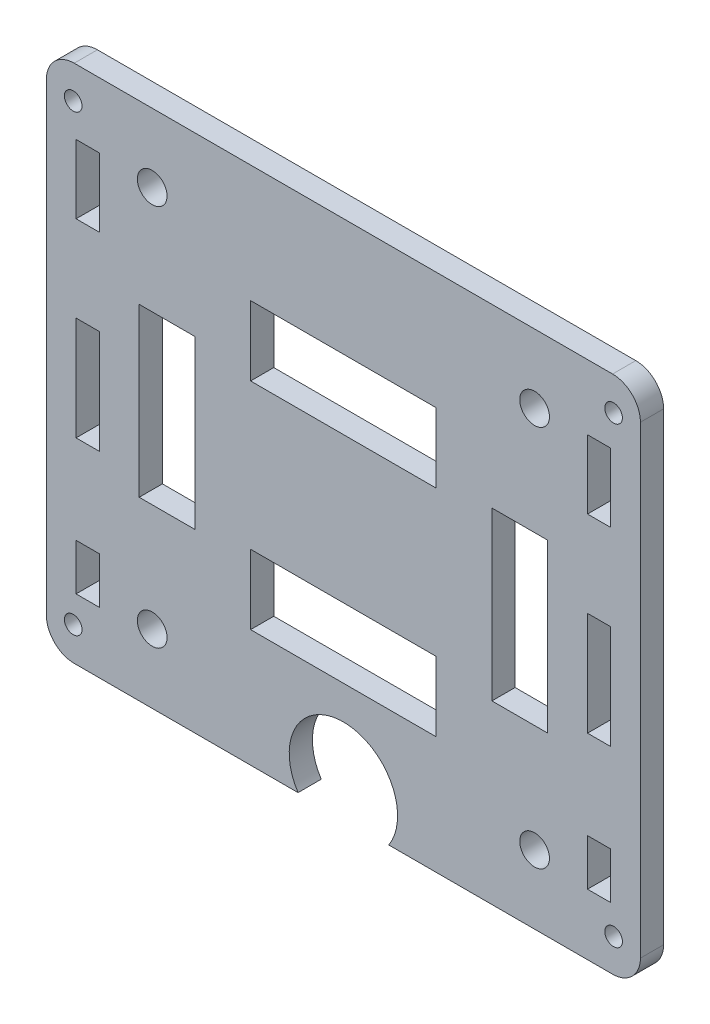
SolidWorks part; units mm, degrees
material "Delrin 2700 NC010, Low Viscosity Acetal Copolymer (SS)"
ref_plane "Front Plane" through (0, 0, 0) normal (0, 0, 1) x (1, 0, 0)
ref_plane "Top Plane" through (0, 0, 0) normal (0, 1, 0) x (1, 0, 0)
ref_plane "Right Plane" through (0, 0, 0) normal (1, 0, 0) x (0, 0, -1)
sketch "Sketch1" plane through (0, 0, 0) normal (0, 0, 1) x (1, 0, 0)
  line L0 (0, -1000) -> (0, 49000) construction
  line L1 (18.415, 17.78) -> (-18.415, 17.78)
  line L2 (20.32, 15.875) -> (20.32, -17.78)
  line L3 (20.32, -17.78) -> (-20.32, -17.78)
  line L4 (-20.32, 15.875) -> (-20.32, -17.78)
  line L5 (20.32, 17.78) -> (-20.32, -17.78) construction
  line L6 (20.32, -17.78) -> (-20.32, 17.78) construction
  line L7 (-1000, 0) -> (49000, 0) construction
  line L9 (10.16, 5.715) -> (13.97, 5.715)
  line L10 (-6.35, -4.9848) -> (6.35, -4.9848)
  line L11 (-6.35, -4.9848) -> (-6.35, -9.7473)
  line L12 (-6.35, -9.7473) -> (6.35, -9.7473)
  line L13 (6.35, -4.9848) -> (6.35, -9.7473)
  line L14 (-6.35, -4.9848) -> (6.35, -9.7473) construction
  line L18 (0, 0) -> (-24.2469, 20.3456) construction
  line L19 (-6.35, -9.7473) -> (6.35, -4.9848) construction
  line L20 (-10.16, 5.715) -> (-13.97, 5.715)
  line L21 (-10.16, 5.715) -> (-10.16, -5.715)
  line L22 (-18.288, 8.625) -> (-16.7005, 8.625)
  line L23 (-18.288, 11.165) -> (-18.288, 8.625)
  line L24 (-16.7005, 11.165) -> (-18.288, 11.165)
  line L25 (-16.7005, 8.625) -> (-16.7005, 11.165)
  line L26 (-10.16, -5.715) -> (-13.97, -5.715)
  line L27 (-13.97, 5.715) -> (-13.97, -5.715)
  line L28 (-10.16, 5.715) -> (-13.97, -5.715) construction
  line L29 (-10.16, -5.715) -> (-13.97, 5.715) construction
  line L30 (10.16, -5.715) -> (13.97, -5.715)
  line L31 (13.97, 5.715) -> (13.97, -5.715)
  line L32 (10.16, 5.715) -> (10.16, -5.715)
  line L33 (-6.35, 4.9848) -> (-6.35, 9.7473)
  line L34 (-6.35, 4.9848) -> (6.35, 4.9848)
  line L35 (-6.35, 9.7473) -> (6.35, 9.7473)
  line L36 (6.35, 4.9848) -> (6.35, 9.7473)
  line L37 (-18.288, 8.625) -> (-16.7005, 8.625)
  line L38 (-18.288, 13.324) -> (-18.288, 8.625)
  line L39 (-16.7005, 11.165) -> (-18.288, 11.165) construction
  line L40 (-16.7005, 8.625) -> (-16.7005, 13.324)
  line L41 (-18.288, -12.457) -> (-16.7005, -12.457)
  line L42 (-18.288, -10.425) -> (-18.288, -12.457)
  line L43 (-16.7005, -10.425) -> (-18.288, -10.425)
  line L44 (-16.7005, -12.457) -> (-16.7005, -10.425)
  line L45 (-18.288, -12.457) -> (-16.7005, -12.457) construction
  line L46 (-18.288, -10.425) -> (-18.288, -13.6)
  line L47 (-16.7005, -10.425) -> (-18.288, -10.425)
  line L48 (-16.7005, -13.6) -> (-16.7005, -10.425)
  line L61 (-18.288, -13.6) -> (-16.7005, -13.6)
  line L62 (-16.7005, 13.324) -> (-18.288, 13.324)
  line L63 (18.288, -12.457) -> (16.7005, -12.457) construction
  line L64 (18.288, -13.6) -> (16.7005, -13.6)
  line L65 (16.7005, -13.6) -> (16.7005, -10.425)
  line L66 (16.7005, -10.425) -> (18.288, -10.425)
  line L67 (18.288, -10.425) -> (18.288, -13.6)
  line L68 (16.7005, 11.165) -> (18.288, 11.165) construction
  line L69 (16.7005, 13.324) -> (18.288, 13.324)
  line L70 (16.7005, 8.625) -> (16.7005, 13.324)
  line L71 (18.288, 13.324) -> (18.288, 8.625)
  line L72 (18.288, 8.625) -> (16.7005, 8.625)
  line L107 (18.288, 2.7432) -> (16.7005, 2.7432)
  line L108 (18.288, -4.3561) -> (16.7005, -4.3561)
  line L109 (18.288, 2.7432) -> (18.288, -4.3561)
  line L110 (16.7005, -4.3561) -> (16.7005, 2.7432)
  line L111 (-16.7005, -4.3561) -> (-16.7005, 2.7432)
  line L112 (-18.288, 2.7432) -> (-18.288, -4.3561)
  line L113 (-18.288, -4.3561) -> (-16.7005, -4.3561)
  line L114 (-18.288, 2.7432) -> (-16.7005, 2.7432)
  circle A0 centre (0, -15.748) radius 3.7084
  circle A1 centre (-18.4847, 15.5105) radius 0.6032
  circle A2 centre (-13.08, -13.08) radius 1.016
  circle A3 centre (18.4847, 15.5105) radius 0.6033
  circle A4 centre (-13.08, 13.08) radius 1.016
  circle A5 centre (13.08, 13.08) radius 1.016
  circle A6 centre (13.08, -13.08) radius 1.016
  arc A7 (18.415, -17.78) -> (20.32, -15.875) centre (18.415, -15.875) ccw
  arc A8 (-18.415, -17.78) -> (-20.32, -15.875) centre (-18.415, -15.875) cw
  arc A9 (-18.415, 17.78) -> (-20.32, 15.875) centre (-18.415, 15.875) ccw
  arc A10 (18.415, 17.78) -> (20.32, 15.875) centre (18.415, 15.875) cw
  circle A11 centre (18.4847, -15.5105) radius 0.6033
  circle A12 centre (-18.4847, -15.5105) radius 0.6032
  point P0 (0, 0)
  point P9 (0, 0)
  point P11 (0, -7.366)
  point P53 (-12.065, 0)
  dimension "D6" = 7.4168
  dimension "D7" = 1.2065
  dimension "D9" = 2.032
  dimension "D12" = 0
  dimension "D13" = 0
  dimension "D14" = 1.905
  dimension "D15" = 1.905
  dimension "D1" = 35.56
  dimension "D2" = 40.64
  dimension "D3" = 4.7625
  dimension "D4" = 12.7
  dimension "D5" = 15.748
  dimension "D8" = 24.13
  dimension "D10" = 13.08
  dimension "D11" = 13.08
  dimension "D17" = 2.159
  dimension "D18" = 7.0993
  dimension "D16" = 1.143
  dimension "D19" = 40
  dimension "D20" = 8.382
  dimension "D21" = 3.81
  dimension "D22" = 11.43
  dimension "D23" = 12.065
  dimension "D24" = 1.5875
  dimension "D25" = 2.7432
extrude "Boss-Extrude1" add sketch "Sketch1" along normal blind 1.5875 contours A10 L1 A9 L4 L3 A0 L2 A6 A5 A4 L12 A1 A2 A3 region at (0, 0.4596, 0)
ref_axis "Axis1" through (0, 0, 0) along (0, 0, 1)
